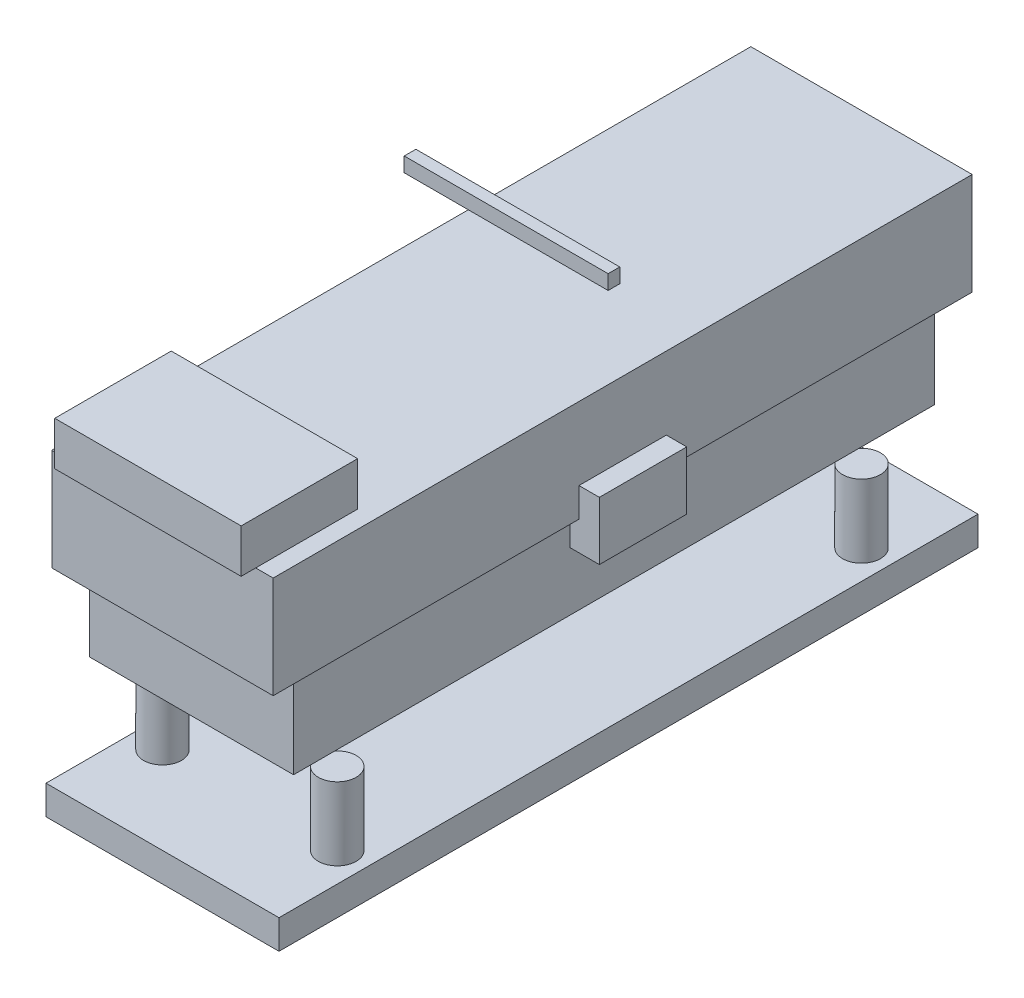
SolidWorks part; units mm, degrees
ref_plane "Front Plane" through (0, 0, 0) normal (0, 0, 1) x (1, 0, 0)
ref_plane "Top Plane" through (0, 0, 0) normal (0, 1, 0) x (1, 0, 0)
ref_plane "Right Plane" through (0, 0, 0) normal (1, 0, 0) x (0, 0, -1)
other "Configuration Table"
sketch "Sketch1" plane through (0, 0, 0) normal (0, 1, 0) x (1, 0, 0)
  line L1 (-400, 0) -> (400, 0)
  line L2 (-400, 0) -> (-400, 2400)
  line L3 (-400, 2400) -> (400, 2400)
  line L4 (400, 0) -> (400, 2400)
extrude "Boss-Extrude1" add sketch "Sketch1" along normal blind 100
sketch "Sketch2" plane through (0, 0, 0) normal (0, 1, 0) x (1, 0, 0)
  circle A0 centre (-300, 300) radius 65
extrude "Boss-Extrude2" add sketch "Sketch2" along normal blind 250 from offset 100
sketch "Sketch3" plane through (0, 0, 0) normal (0, 1, 0) x (1, 0, 0)
  circle A0 centre (300, 300) radius 65
extrude "Boss-Extrude3" add sketch "Sketch3" along normal blind 250 from offset 100
sketch "Sketch4" plane through (0, 0, 0) normal (0, 1, 0) x (1, 0, 0)
  circle A0 centre (-300, 2100) radius 65
extrude "Boss-Extrude4" add sketch "Sketch4" along normal blind 250 from offset 100
sketch "Sketch5" plane through (0, 0, 0) normal (0, 1, 0) x (1, 0, 0)
  circle A0 centre (300, 2100) radius 65
extrude "Boss-Extrude5" add sketch "Sketch5" along normal blind 250 from offset 100
sketch "Sketch6" plane through (0, 0, 0) normal (0, 1, 0) x (1, 0, 0)
  line L1 (-350, 100) -> (350, 100)
  line L2 (-350, 100) -> (-350, 2300)
  line L3 (-350, 2300) -> (350, 2300)
  line L4 (350, 100) -> (350, 2300)
extrude "Boss-Extrude6" add sketch "Sketch6" along normal blind 400 from offset 450
sketch "Sketch7" plane through (0, 0, 0) normal (0, 1, 0) x (1, 0, 0)
  circle A0 centre (0, 1200) radius 60
extrude "Boss-Extrude7" add sketch "Sketch7" against normal blind 150 from offset 450 flip side to cut
sketch "Sketch8" plane through (0, 0, 0) normal (0, 1, 0) x (1, 0, 0)
  line L0 (-400, 0) -> (400, 0) construction
  line L1 (-380, 0) -> (380, 0)
  line L2 (-380, 0) -> (-380, 2400)
  line L3 (-380, 2400) -> (380, 2400)
  line L4 (380, 0) -> (380, 2400)
  line L5 (400, 2400) -> (-400, 2400) construction
extrude "Boss-Extrude8" add sketch "Sketch8" along normal blind 350 from offset 750
sketch "Sketch9" plane through (0, 0, 0) normal (0, 1, 0) x (1, 0, 0)
  line L1 (-320, -50) -> (320, -50)
  line L2 (-320, -50) -> (-320, 350)
  line L3 (-320, 350) -> (320, 350)
  line L4 (320, -50) -> (320, 350)
extrude "Boss-Extrude9" add sketch "Sketch9" along normal blind 150 from offset 1100
sketch "Sketch10" plane through (0, 0, 0) normal (0, 1, 0) x (1, 0, 0)
  line L1 (-350, 1180) -> (350, 1180)
  line L2 (-350, 1180) -> (-350, 1220)
  line L3 (-350, 1220) -> (350, 1220)
  line L4 (350, 1180) -> (350, 1220)
extrude "Boss-Extrude10" add sketch "Sketch10" along normal blind 50 from offset 1350
sketch "Sketch11" plane through (0, 0, 0) normal (0, 1, 0) x (1, 0, 0)
  line L1 (-450, 1050) -> (450, 1050)
  line L2 (-450, 1050) -> (-450, 1350)
  line L3 (-450, 1350) -> (450, 1350)
  line L4 (450, 1050) -> (450, 1350)
extrude "Boss-Extrude11" add sketch "Sketch11" along normal blind 200 from offset 650
